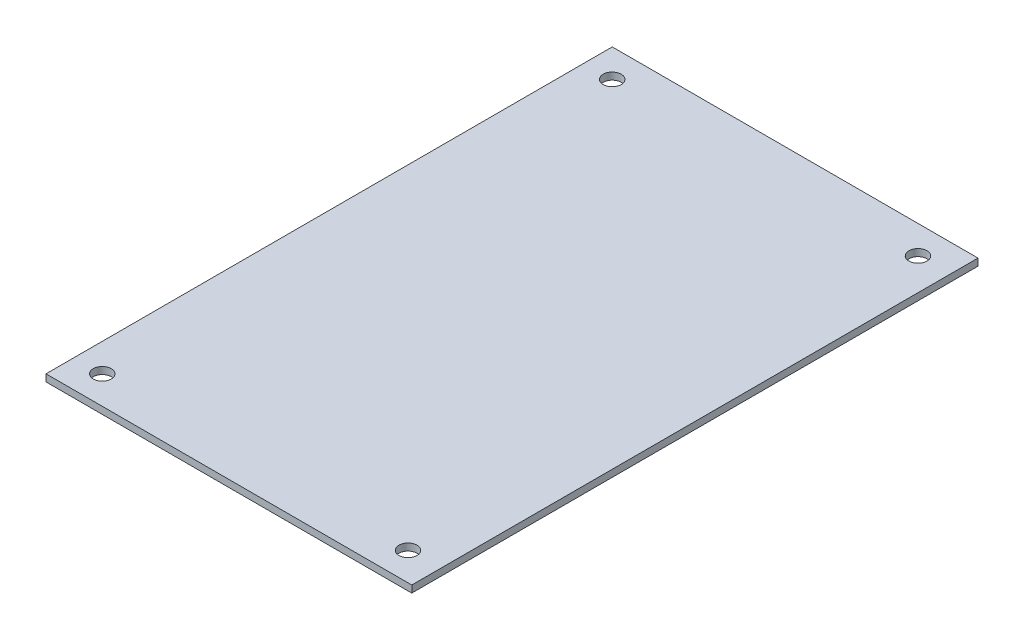
SolidWorks part; units mm, degrees
material "Balsa"
ref_plane "Front Plane" through (0, 0, 0) normal (0, 0, 1) x (1, 0, 0)
ref_plane "Top Plane" through (0, 0, 0) normal (0, 1, 0) x (1, 0, 0)
ref_plane "Right Plane" through (0, 0, 0) normal (1, 0, 0) x (0, 0, -1)
sketch "Sketch3" plane through (0, 0, 0) normal (0, 0, 1) x (1, 0, 0)
  line L1 (0, 0) -> (330.2, 0)
  line L2 (0, 0) -> (0, 6.35)
  line L3 (0, 6.35) -> (330.2, 6.35)
  line L4 (330.2, 0) -> (330.2, 6.35)
  dimension "D1" = 6.35
  dimension "D2" = 330.2
extrude "Boss-Extrude1" add sketch "Sketch3" against normal blind 511.175
sketch "Sketch4" plane through (0, 0, 0) normal (0, 1, 0) x (1, 0, 0)
  line L0 (0, 0) -> (330.2, 0) construction
  line L1 (163.3996, 0) -> (163.3996, 511.175) construction
  line L2 (330.2, 511.175) -> (0, 511.175) construction
  line L3 (163.3996, 511.175) -> (330.2, 511.175) construction
  line L4 (330.2, 511.175) -> (0, 511.175) construction
  line L5 (0, 511.175) -> (163.3996, 511.175) construction
  line L6 (0, -3.4925) -> (0, 3.4925) construction
  line L7 (163.3996, 255.5875) -> (0, 255.5875) construction
  line L8 (0, 511.175) -> (0, 0) construction
  line L9 (0, 255.5875) -> (330.2, 255.5875) construction
  line L10 (330.2, 511.175) -> (330.2, 0) construction
  circle A0 centre (25.4, 25.4) radius 8.128
  circle A1 centre (301.3991, 25.4) radius 8.128
  circle A2 centre (301.3991, 485.775) radius 8.128
  circle A3 centre (25.4, 485.775) radius 8.128
  dimension "D1" = 16.256
  dimension "D2" = 25.4
  dimension "D3" = 25.4
extrude "Cut-Extrude1" cut sketch "Sketch4" along normal through all
